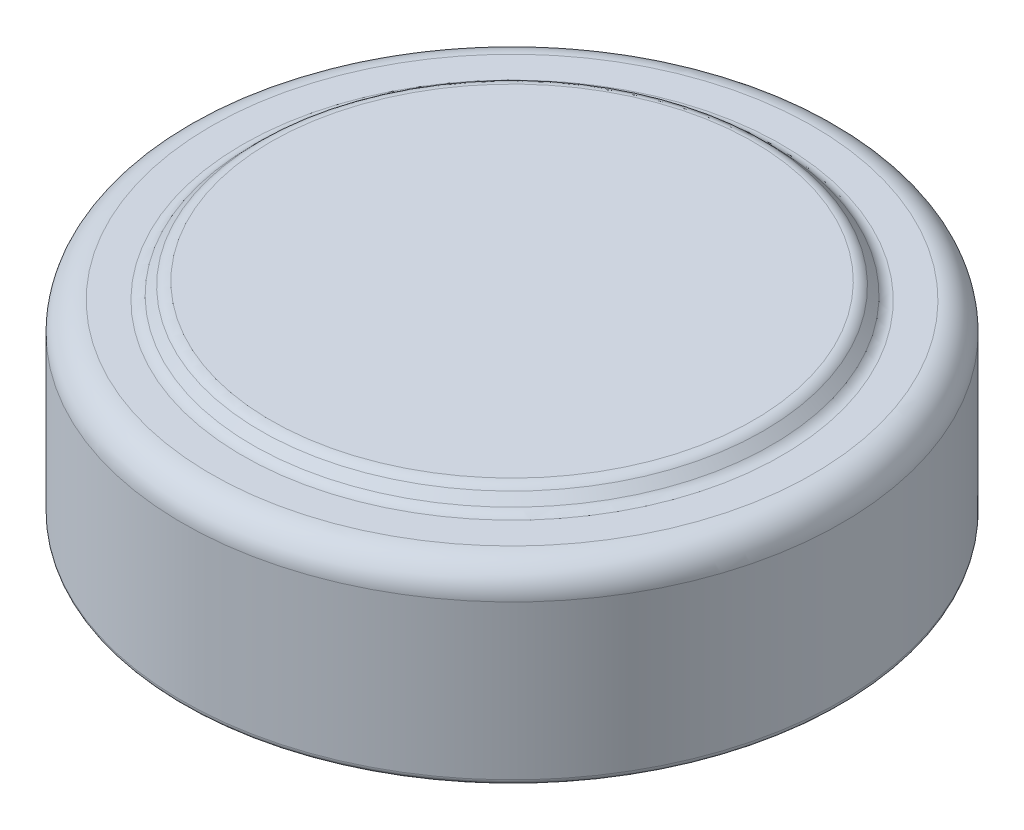
SolidWorks part; units mm, degrees
ref_plane "Front Plane" through (0, 0, 0) normal (0, 0, 1) x (1, 0, 0)
ref_plane "Top Plane" through (0, 0, 0) normal (0, 1, 0) x (1, 0, 0)
ref_plane "Right Plane" through (0, 0, 0) normal (1, 0, 0) x (0, 0, -1)
sketch "Sketch1" plane through (0, 0, 0) normal (0, 0, 1) x (1, 0, 0)
  line L0 (0, 0) -> (-5.7, 0)
  line L1 (-5.8, 0.1) -> (-5.8, 2.81)
  line L2 (-4.2464, 3.6) -> (0, 3.6)
  line L3 (0, 3.6) -> (0, 0)
  line L4 (-4.4232, 3.5268) -> (-4.5668, 3.3832)
  line L7 (-5.3, 3.31) -> (-4.7436, 3.31)
  arc A0 (-5.8, 2.81) -> (-5.3, 3.31) centre (-5.3, 2.81) cw
  arc A1 (-4.2464, 3.6) -> (-4.4232, 3.5268) centre (-4.2464, 3.35) ccw
  arc A2 (-4.7436, 3.31) -> (-4.5668, 3.3832) centre (-4.7436, 3.56) ccw
  arc A3 (-5.7, 0) -> (-5.8, 0.1) centre (-5.7, 0.1) cw
  point P9 (-5.8, 3.31)
  point P14 (-4.64, 3.31)
  point P17 (-5.8, 0)
  point P18 (-4.35, 3.6)
  dimension "D6" = 0.5
  dimension "D7" = 0.25
  dimension "D8" = 0.1
  dimension "D5" = 45
  dimension "D1" = 5.8
  dimension "D2" = 3.6
  dimension "D3" = 4.64
  dimension "D4" = 3.31
revolve "Revolve1" add sketch "Sketch1" angle 360 about L3
sketch "Sketch2" plane through (0, 0, 0) normal (0, -1, 0) x (1, 0, 0)
  line L0 (0.25, 0.25) -> (2, 0.25)
  line L1 (-0.25, 2) -> (0.25, 2)
  line L2 (-0.25, 2) -> (-0.25, 0.25)
  line L3 (-0.25, -2) -> (0.25, -2)
  line L4 (0.25, 2) -> (0.25, 0.25)
  line L5 (-2, 0.25) -> (-0.25, 0.25)
  line L6 (-2, 0.25) -> (-2, -0.25)
  line L7 (-2, -0.25) -> (-0.25, -0.25)
  line L8 (2, 0.25) -> (2, -0.25)
  line L9 (0.25, -0.25) -> (2, -0.25)
  line L10 (0.25, -0.25) -> (0.25, -2)
  line L11 (-0.25, -0.25) -> (-0.25, -2)
  circle A0 centre (0, 0) radius 4 construction
  text T0 "                                 SR42" font "Century Gothic" height 1
  dimension "D1" = 8
  dimension "D2" = 0.5
  dimension "D3" = 0.25
  dimension "D4" = 0.5
  dimension "D5" = 0.25
  dimension "D6" = 4
  dimension "D7" = 4
  dimension "D8" = 2
  dimension "D9" = 2
wrap "Wrap1" sketch "Sketch2" wrap type scribe source sketch "Sketch2" face at (-5.7, 0, 0)
